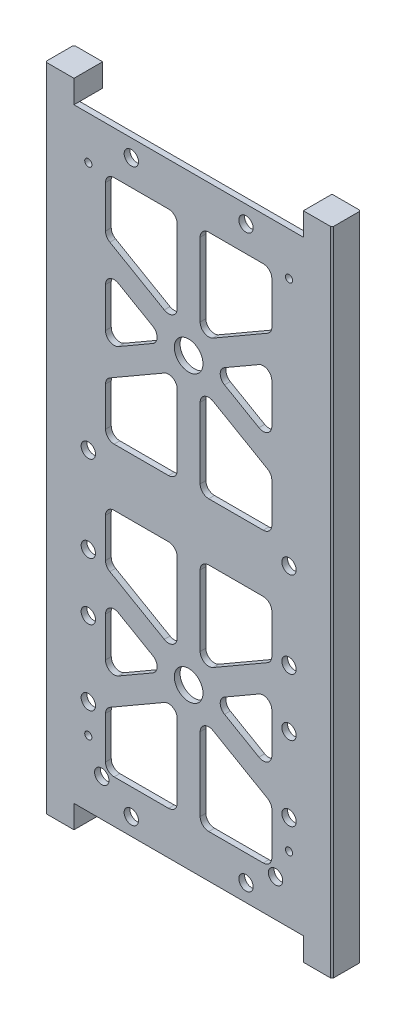
SolidWorks part; units mm, degrees
material "6061-T6 (SS)"
ref_plane "Front Plane" through (0, 0, 0) normal (0, 0, 1) x (1, 0, 0)
ref_plane "Top Plane" through (0, 0, 0) normal (0, 1, 0) x (1, 0, 0)
ref_plane "Right Plane" through (0, 0, 0) normal (1, 0, 0) x (0, 0, -1)
sketch "Sketch1" plane through (0, 0, 0) normal (0, 0, 1) x (1, 0, 0)
  line L1 (0, 0) -> (88, 0)
  line L2 (0, 0) -> (0, 211)
  line L3 (0, 211) -> (88, 211)
  line L4 (88, 0) -> (88, 211)
  dimension "D1" = 88
  dimension "D2" = 211
extrude "Boss-Extrude1" add sketch "Sketch1" along normal blind 2
sketch "Sketch2" plane through (0, 0, 2) normal (0, 0, 1) x (1, 0, 0)
  line L0 (0, 105.5) -> (88, 105.5) construction
  line L1 (0, 211) -> (0, 0) construction
  line L2 (88, 0) -> (88, 211) construction
  line L3 (44, 211) -> (44, 0) construction
  line L4 (88, 211) -> (0, 211) construction
  line L5 (0, 0) -> (88, 0) construction
  line L6 (0, 155.25) -> (88, 155.25) construction
  line L7 (0, 55.75) -> (88, 55.75) construction
  dimension "D1" = 55.75
  dimension "D2" = 55.75
sketch "Sketch3" plane through (0, 0, 2) normal (0, 0, 1) x (1, 0, 0)
  line L0 (0, 155.25) -> (88, 155.25) construction
  line L2 (0, 211) -> (0, 0) construction
  line L3 (15, 196) -> (73, 196)
  line L4 (15, 196) -> (15, 115.5)
  line L5 (15, 115.5) -> (73, 115.5)
  line L6 (73, 196) -> (73, 115.5)
  line L7 (88, 211) -> (0, 211) construction
  line L8 (88, 0) -> (88, 211) construction
  line L9 (0, 105.5) -> (88, 105.5) construction
  line L10 (40, 196) -> (40, 115.5)
  line L11 (48, 196) -> (48, 115.5)
  line L12 (44, 211) -> (44, 0) construction
  line L13 (73, 171.9932) -> (15, 138.5068) construction
  line L14 (15, 171.9932) -> (73, 138.5068) construction
  line L15 (73, 176.612) -> (15, 143.1256)
  line L16 (73, 167.3744) -> (15, 133.888)
  line L17 (15, 176.612) -> (73, 143.1256)
  line L18 (15, 167.3744) -> (73, 133.888)
  circle A0 centre (44, 155.25) radius 5
  dimension "D1" = 10
  dimension "D3" = 15
  dimension "D4" = 15
  dimension "D5" = 15
  dimension "D6" = 10
  dimension "D7" = 8
  dimension "D8" = 4
  dimension "D9" = 30
  dimension "D10" = 30
  dimension "D11" = 8
  dimension "D12" = 4
  dimension "D13" = 4
  dimension "D14" = 8
ref_plane "Plane1" through (0, 105.5, 0) normal (0, -1, 0) x (1, 0, 0)
extrude "Cut-Extrude2" cut sketch "Sketch3" against normal blind 2 contours L18 L11 L5 L6 | L10 L16 L4 L5 | L18 L4 L15 | L16 L17 L6 | L15 L6 L3 L11 | L4 L17 L10 L3 region at (28.6303, 182.3713, 2) region at (59.3697, 182.3713, 2) region at (22, 155.25, 2) region at (28.6744, 128.6415, 2) region at (66, 155.25, 2) region at (59.3256, 128.6415, 2)
sketch "Sketch4" plane through (0, 0, 2) normal (0, 0, 1) x (1, 0, 0)
  line L0 (0, 155.25) -> (88, 155.25) construction
  circle A0 centre (44, 155.25) radius 5
  dimension "D1" = 10
extrude "Cut-Extrude3" cut sketch "Sketch4" against normal through all
mirror "Mirror2" about plane through (0, 105.5, 0) normal (0, -1, 0) of "Cut-Extrude3", "Cut-Extrude2"
fillet "Fillet2" radius 3 44 edges at (73, 67.8744, 1) (73, 43.6256, 1) (52, 55.75, 1) (40, 48.8218, 1) (40, 15, 1) (15, 15, 1) (15, 34.388, 1) (15, 143.1256, 1) (15, 167.3744, 1) (36, 155.25, 1) (15, 115.5, 1) (15, 133.888, 1) (40, 148.3218, 1) (40, 115.5, 1) (48, 196, 1) (73, 196, 1) (48, 162.1782, 1) (73, 115.5, 1) (48, 115.5, 1) (48, 148.3218, 1) (73, 133.888, 1) (15, 196, 1) (40, 196, 1) (40, 162.1782, 1) (15, 176.612, 1) (73, 167.3744, 1) (73, 143.1256, 1) (52, 155.25, 1) (48, 62.6782, 1) (48, 95.5, 1) (73, 95.5, 1) (73, 77.112, 1) (73, 34.388, 1) (73, 15, 1) (48, 15, 1) (48, 48.8218, 1) (40, 62.6782, 1) (15, 77.112, 1) (15, 95.5, 1) (40, 95.5, 1) (15, 43.6256, 1) (15, 67.8744, 1) (36, 55.75, 1) (73, 176.612, 1)
sketch "Sketch5" plane through (0, 0, 2) normal (0, 0, 1) x (1, 0, 0)
  line L0 (88, 0) -> (88, 211) construction
  line L1 (0, 211) -> (0, 0) construction
  line L4 (0, 5.5) -> (88, 5.5) construction
  line L5 (0, 0) -> (88, 0) construction
  line L6 (0, 205.5) -> (88, 205.5) construction
  circle A1 centre (64, 205.5) radius 1.5
  circle A3 centre (64, 5.5) radius 1.5
  circle A4 centre (24, 5.5) radius 1.5
  circle A5 centre (24, 205.5) radius 1.5
  dimension "D5" = 3
  dimension "D2" = 40
  dimension "D3" = 24
  dimension "D1" = 200
  dimension "D4" = 5.5
  dimension "D6" = 3
  dimension "D7" = 40
  dimension "D8" = 24
  dimension "D9" = 3
  dimension "D10" = 24
  dimension "D11" = 24
  dimension "D12" = 3
sketch "Sketch7" plane through (0, 0, 2) normal (0, 0, 1) x (1, 0, 0)
  line L0 (0, 105.5) -> (151.3859, 105.5) construction
  line L5 (0, 211) -> (0, 0) construction
  line L7 (44, 211) -> (44, 0) construction
  line L8 (88, 211) -> (0, 211) construction
  line L9 (0, 0) -> (88, 0) construction
  line L17 (94, 219) -> (84, 219)
  line L53 (88, 0) -> (88, 211)
  line L54 (84, 219) -> (84, 211)
  line L55 (84, 0) -> (88, 0)
  line L56 (94, 0) -> (94, 211)
  line L57 (94, -8) -> (94, 219)
  line L58 (88, 211) -> (0, 211) construction
  line L59 (84, 211) -> (88, 211)
  line L60 (84, -8) -> (84, 0)
  line L61 (94, -8) -> (84, -8)
  line L62 (-6, -8) -> (4, -8)
  line L63 (4, -8) -> (4, 0)
  line L64 (4, 0) -> (0, 0)
  line L65 (0, 0) -> (0, 211)
  line L66 (4, 211) -> (0, 211)
  line L67 (4, 219) -> (4, 211)
  line L68 (-6, 219) -> (4, 219)
  line L69 (-6, -8) -> (-6, 219)
  dimension "D1" = 6
extrude "Boss-Extrude2" add sketch "Sketch7" against normal blind 10
sketch "Sketch53" plane through (0, 0, -8) normal (0, 0, -1) x (-1, 0, 0)
  line L0 (-84, 0) -> (-84, 211)
  line L1 (-84, 211) -> (-90, 211)
  line L2 (-92, 209) -> (-92, 2)
  line L4 (-44, 0) -> (-44, 211)
  line L5 (-4, 0) -> (-84, 0) construction
  line L6 (-84, 211) -> (-4, 211) construction
  line L8 (-90, 0) -> (-84, 0)
  line L9 (4, 209) -> (4, 2)
  line L10 (-4, 211) -> (2, 211)
  line L11 (-4, 0) -> (-4, 211)
  line L12 (2, 0) -> (-4, 0)
  arc A0 (-92, 209) -> (-90, 211) centre (-90, 209) cw
  arc A1 (-90, 0) -> (-92, 2) centre (-90, 2) cw
  arc A2 (4, 209) -> (2, 211) centre (2, 209) ccw
  arc A3 (2, 0) -> (4, 2) centre (2, 2) ccw
  line M9 (-88, 0) -> (-88, 211)
  dimension "D1" = 2
  dimension "D2" = 2
extrude "Cut-Extrude5" cut sketch "Sketch53" against normal blind 8 contours A1 L8 L1 A0 L2 M9 | L12 A3 L9 A2 L10 L11 region at (89.9968, 105.5, -8) region at (0.0036, 105.5, -8)
ref_plane "Plane2" through (44, 0, 0) normal (-1, 0, 0) x (0, 0, 1)
ref_plane "Plane3" through (44, 0, 0) normal (1, 0, 0) x (0, 0, -1)
sketch "Sketch58" plane through (0, 0, 0) normal (0, 0, -1) x (-1, 0, 0)
  line L0 (-4, 0) -> (-84, 0) construction
  line L4 (4, 209) -> (4, 2) construction
  circle A0 centre (-0.7, 13) radius 1.665
  dimension "D1" = 3.33
  dimension "D2" = 4.7
  dimension "D3" = 13
extrude "Cut-Extrude9" cut sketch "Sketch58" against normal blind 1.8 contours A0
mirror "Mirror4" about plane through (44, 0, 0) normal (1, 0, 0) of "Cut-Extrude9"
sketch "Sketch59" plane through (0, -8, 0) normal (0, -1, 0) x (-1, 0, 0)
  line L0 (-94, 8) -> (-94, -2) construction
  line L1 (6, 8) -> (6, -2) construction
  line L2 (-84, 8) -> (-94, 8) construction
  circle A0 centre (-89, 2.4) radius 2
  circle A1 centre (1, 2.4) radius 2
  dimension "D1" = 4
  dimension "D2" = 5
  dimension "D3" = 5
  dimension "D4" = 5.6
extrude "Cut-Extrude10" cut sketch "Sketch59" against normal blind 10
fillet "Fillet3" radius 0.5 4 edges at (-6, 105.5, 2) (-6, 105.5, -8) (94, 105.5, -8) (94, 105.5, 2) profile chamfer
sketch "Sketch60" plane through (0, 0, 2) normal (0, 0, 1) x (1, 0, 0)
  line L0 (44, 211) -> (44, 0) construction
  line L1 (84, 211) -> (4, 211) construction
  line L2 (4, 0) -> (84, 0) construction
  line L3 (-5.5, 219) -> (-5.5, -8) construction
  line L4 (-4, 209) -> (-4, 2) construction
  point P8 (64, 6)
  point P9 (74.3, 13)
  point P10 (79, 23)
  point P11 (79, 33.2)
  point P12 (79, 59.2)
  point P13 (79, 79.2)
  point P14 (9, 196)
  point P15 (9, 79.2)
  point P16 (9, 109.2)
  point P17 (79, 109.2)
  point P18 (9, 59.2)
  point P19 (9, 33.2)
  point P20 (24, 205)
  point P23 (9, 23)
  point P24 (79, 196)
  point P25 (64, 205)
  point P27 (13.7, 13)
  point P28 (24, 6)
  dimension "D1" = 6
  dimension "D2" = 29.5
  dimension "D3" = 15
  dimension "D4" = 14.5
  dimension "D5" = 14.5
  dimension "D6" = 101.8
  dimension "D7" = 131.8
  dimension "D8" = 14.5
  dimension "D9" = 151.8
  dimension "D10" = 14.5
  dimension "D11" = 14.5
  dimension "D12" = 177.8
  dimension "D13" = 188
  dimension "D14" = 14.5
  dimension "D15" = 198
  dimension "D16" = 17.7
  dimension "D17" = 205
  dimension "D18" = 29.5
hole_wizard "Ø5.0mm Dowel Hole1" positions "Sketch61" profile "Sketch62" hole size "Ø5.0" standard "ANSI Metric" end condition through all
sketch "Sketch61" plane through (0, 0, 2) normal (0, 0, 1) x (1, 0, 0)
  point P0 (24, 205)
  point P3 (64, 205)
  point P6 (9, 109.2)
  point P9 (79, 109.2)
  point P12 (9, 79.2)
  point P15 (79, 79.2)
  point P18 (9, 59.2)
  point P21 (79, 59.2)
  point P24 (9, 33.2)
  point P27 (79, 33.2)
  point P30 (13.7, 13)
  point P33 (24, 6)
  point P36 (74.3, 13)
  point P39 (64, 6)
sketch "Sketch62" plane through (24, 205, 2) normal (1, 0, 0) x (0, -1, 0)
  line L0 (0, 0) -> (0, 10)
  line L1 (0, 10) -> (2.5, 10)
  line L2 (2.5, 10) -> (2.5, 0)
  line L5 (2.5, 0) -> (0, 0)
  line L11 (0, -6.35) -> (0, 107.95) construction
  dimension "Thru Hole Dia." = 5
  dimension "Thru Hole Depth" = 10
hole_wizard "Tap Drill for M3x0.5 Tap1" positions "Sketch63" profile "Sketch64" hole size "M3x0.5" standard "ANSI Metric" end condition through all
sketch "Sketch63" plane through (0, 0, 2) normal (0, 0, 1) x (1, 0, 0)
  point P0 (9, 196)
  point P3 (79, 196)
  point P6 (9, 23)
  point P9 (79, 23)
sketch "Sketch64" plane through (9, 196, 2) normal (1, 0, 0) x (0, -1, 0)
  line L0 (0, 0) -> (0, 10)
  line L1 (0, 10) -> (1.25, 10)
  line L2 (1.25, 10) -> (1.25, 0)
  line L5 (1.25, 0) -> (0, 0)
  line L11 (0, -6.35) -> (0, 107.95) construction
  dimension "Thru Hole Dia." = 2.5
  dimension "Thru Hole Depth" = 10
